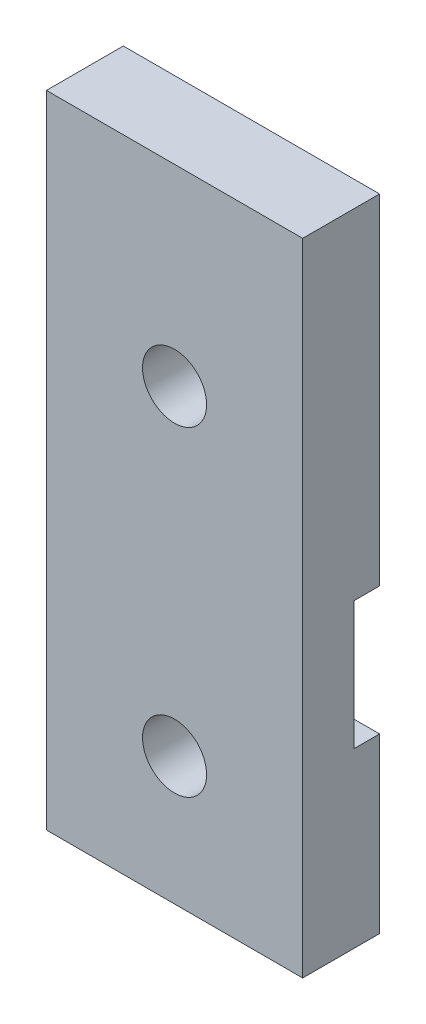
SolidWorks part; units mm, degrees
material "Policarbonato"
ref_plane "Plano frontal" through (0, 0, 0) normal (0, 0, 1) x (1, 0, 0)
ref_plane "Plano superior" through (0, 0, 0) normal (0, 1, 0) x (1, 0, 0)
ref_plane "Plano direito" through (0, 0, 0) normal (1, 0, 0) x (0, 0, -1)
sketch "Esboço1" plane through (0, 0, 0) normal (0, 0, 1) x (1, 0, 0)
  line L1 (0, 0) -> (20, 0)
  line L2 (0, 0) -> (0, 50)
  line L3 (0, 50) -> (20, 50)
  line L4 (20, 0) -> (20, 50)
  dimension "D1" = 20
  dimension "D2" = 50
extrude "Ressalto-extrusão1" add sketch "Esboço1" along normal blind 6
sketch "Esboço2" plane through (0, 0, 0) normal (0, 0, -1) x (-1, 0, 0)
  line L0 (-10, 35) -> (-10, 10) construction
  line L4 (0, 0) -> (0, 50)
  line L5 (0, 50) -> (-20, 50)
  line L6 (-20, 50) -> (-20, 0)
  line L7 (-20, 0) -> (0, 0)
  line L8 (0, 0) -> (0, 50)
  line L9 (0, 50) -> (-20, 50)
  line L10 (-20, 50) -> (-20, 0)
  line L11 (-20, 0) -> (0, 0)
  circle A0 centre (-10, 35) radius 2.5 construction
  circle A1 centre (-10, 35) radius 2.5
  circle A3 centre (-3.25, 18.5) radius 2.5 construction
  circle A5 centre (-3.25, 18.5) radius 2.5
  circle A6 centre (-10, 10) radius 2.5
  dimension "D2" = 10
  dimension "D1" = 0
extrude "Corte-extrusão1" cut sketch "Esboço2" against normal blind 10 contours A1 | A5 | A6 region at (10, 35, 0) region at (3.25, 18.5, 0) region at (10, 10, 0)
sketch "Esboço3" plane through (0, 0, 0) normal (0, 0, 1) x (1, 0, 0)
  line L0 (10, 50) -> (10, 41.4324) construction
  line L1 (20, 50) -> (0, 50) construction
  circle A0 centre (3.25, 18.5) radius 5
  circle A1 centre (16.75, 18.5) radius 5
  dimension "D1" = 10
extrude "Corte-extrusão2" cut sketch "Esboço3" along normal blind 2
sketch "Esboço4" plane through (0, 0, 0) normal (0, 0, -1) x (-1, 0, 0)
  line L0 (-3.25, 23.5) -> (0, 23.5)
  line L1 (0, 50) -> (0, 22.2997) construction
  line L2 (0, 23.5) -> (0, 13.5)
  line L3 (0, 14.7003) -> (0, 0) construction
  line L4 (0, 13.5) -> (-3.25, 13.5)
  line L5 (-3.25, 13.5) -> (-3.25, 23.5)
  line L6 (-10, 50) -> (-10, 41.2912) construction
  line L7 (-20, 50) -> (0, 50) construction
  line L8 (-20, 13.5) -> (-16.75, 13.5)
  line L9 (-20, 23.5) -> (-20, 13.5)
  line L10 (-16.75, 23.5) -> (-20, 23.5)
  line L11 (-16.75, 13.5) -> (-16.75, 23.5)
  arc A0 (0, 22.2997) -> (0, 14.7003) centre (-3.25, 18.5) ccw construction
  arc A1 (0, 22.2997) -> (0, 14.7003) centre (-3.25, 18.5) ccw construction
  point P10 (-3.25, 18.5)
  point P15 (-3.25, 23.5)
extrude "Corte-extrusão3" cut sketch "Esboço4" against normal blind 2
sketch "Esboço5" plane through (0, 0, 6) normal (0, 0, 1) x (1, 0, 0)
  circle A0 centre (3.25, 18.5) radius 2.5 construction
  circle A1 centre (3.25, 18.5) radius 2.5
extrude "Ressalto-extrusão2" add sketch "Esboço5" against normal blind 4
